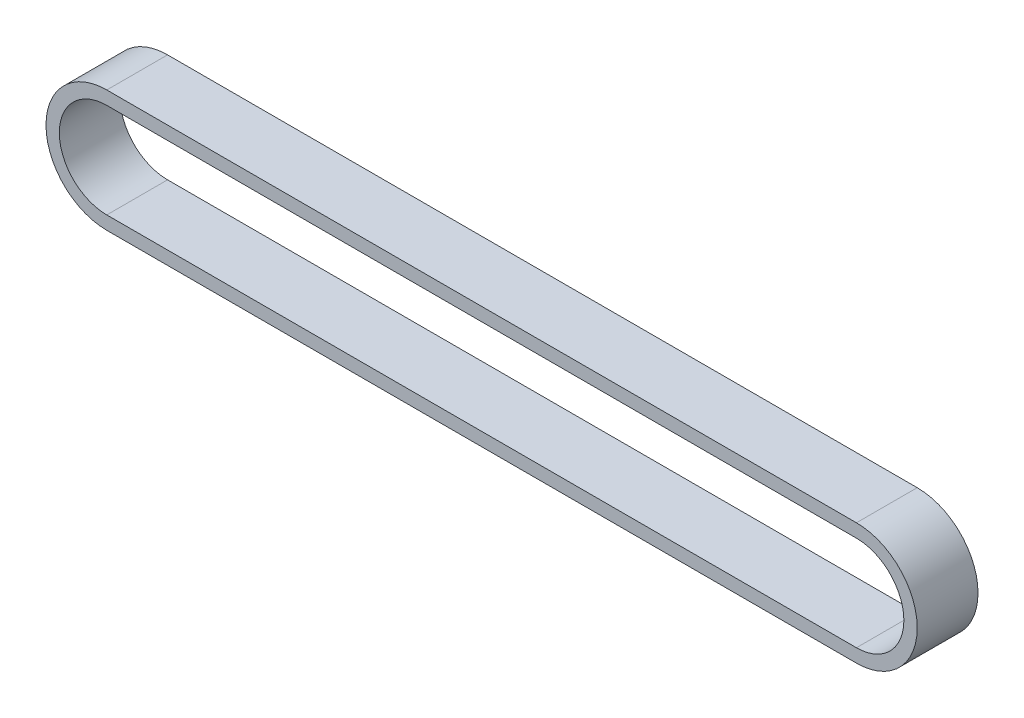
SolidWorks part; units mm, degrees
ref_plane "Front Plane" through (0, 0, 0) normal (0, 0, 1) x (1, 0, 0)
ref_plane "Top Plane" through (0, 0, 0) normal (0, 1, 0) x (1, 0, 0)
ref_plane "Right Plane" through (0, 0, 0) normal (1, 0, 0) x (0, 0, -1)
sketch "Sketch1" plane through (0, 0, 0) normal (0, 0, 1) x (1, 0, 0)
  line L0 (0, 0) -> (-234.95, 0) construction
  line L1 (0, -19.05) -> (-234.95, -19.05)
  line L2 (0, 19.05) -> (-234.95, 19.05)
  line L3 (0, 0) -> (-234.95, 0) construction
  line L4 (0, -14.8683) -> (-234.95, -14.8683)
  line L5 (0, 14.8683) -> (-234.95, 14.8683)
  arc A0 (0, -19.05) -> (0, 19.05) centre (0, 0) ccw
  arc A1 (-234.95, 19.05) -> (-234.95, -19.05) centre (-234.95, 0) ccw
  arc A2 (0, -14.8683) -> (0, 14.8683) centre (0, 0) ccw
  arc A3 (-234.95, 14.8683) -> (-234.95, -14.8683) centre (-234.95, 0) ccw
  point P3 (-117.475, 0)
  point P8 (-117.475, -19.05)
  point P9 (19.05, 0)
  point P12 (-117.475, 0)
  dimension "D2" = 254
  dimension "D1" = 38.1
extrude "Boss-Extrude1" add sketch "Sketch1" along normal blind 19.05
sketch "Sketch6" plane through (0, 0, 19.05) normal (0, 0, 1) x (1, 0, 0)
  line L0 (0, 0) -> (-234.95, 0) construction
  line L1 (0, -6.477) -> (-234.95, -6.477)
  line L2 (0, 6.477) -> (-234.95, 6.477)
  arc A0 (0, -6.477) -> (0, 6.477) centre (0, 0) ccw
  arc A1 (-234.95, 6.477) -> (-234.95, -6.477) centre (-234.95, 0) ccw
  point P4 (-117.475, 0)
  dimension "D1" = 12.954
extrude "Cut-Extrude2" cut sketch "Sketch6" against normal blind 44.958 rebuild error yes
